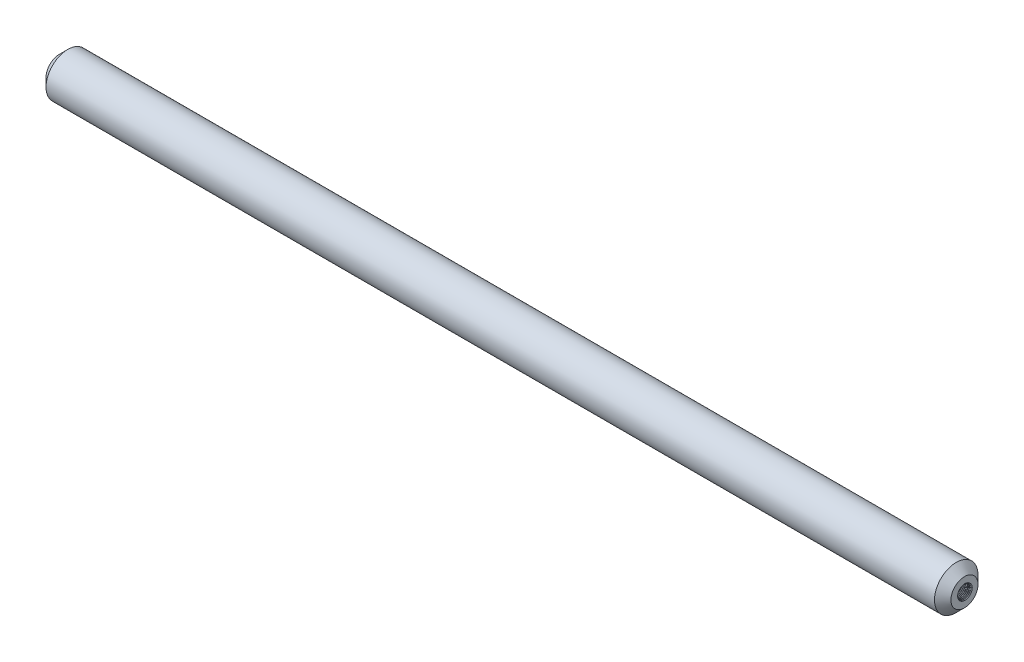
SolidWorks part; units mm, degrees
ref_plane "Front Plane" through (0, 0, 0) normal (0, 0, 1) x (1, 0, 0)
ref_plane "Top Plane" through (0, 0, 0) normal (0, 1, 0) x (1, 0, 0)
ref_plane "Right Plane" through (0, 0, 0) normal (1, 0, 0) x (0, 0, -1)
sketch "Sketch1" plane through (0, 0, 0) normal (1, 0, 0) x (0, 0, -1)
  circle A0 centre (0, 0) radius 7.9375
  dimension "D1" = 15.875
extrude "Boss-Extrude1" add sketch "Sketch1" against normal blind 330
sketch "Sketch2" plane through (0, 0, 0) normal (1, 0, 0) x (0, 0, -1)
  circle A0 centre (0, 0) radius 2.5
  dimension "D1" = 5
extrude "Cut-Extrude1" cut sketch "Sketch2" against normal blind 24
sketch "Sketch3" plane through (-330, 0, 0) normal (-1, 0, 0) x (0, 0, 1)
  circle A0 centre (0, 0) radius 2.5
  dimension "D1" = 5
extrude "Cut-Extrude2" cut sketch "Sketch3" against normal blind 24
sketch "Sketch4" plane through (0, 0, 0) normal (1, 0, 0) x (0, 0, -1)
  circle A0 centre (0, 0) radius 2.5
  dimension "D1" = 5
curve "Helix/Spiral1" pitch 0.5 height 18 radius 2.5 centre (0, 0, 0) axis (-1, 0, 0) start towards (0, 0, -1)
sketch "Sketch5" plane through (0, 0, 0) normal (1, 0, 0) x (0, 0, -1)
  line L1 (2.5, 0) -> (0, 0) construction
  circle A0 centre (0, 0) radius 2.5 construction
sketch3d "3DSketch5"
  point P0 (0, 0, -2.5)
sketch3d "3DSketch6"
  line L0 (0.2, 0, -2.5) -> (-0.2, 0, -2.5)
  line L2 (0.2, 0, -2.5) -> (-0.0014, 0, -2.8472)
  line L3 (-0.0014, 0, -2.8472) -> (-0.2, 0, -2.5)
  point P11 (0, 0, -2.5)
  dimension "D1" = 0.4
  dimension "D2" = 0.4
sweep "Cut-Sweep5" cut profiles "3DSketch6" path "Helix/Spiral1" align with end faces yes
sketch "Sketch8" plane through (-330, 0, 0) normal (-1, 0, 0) x (0, 0, 1)
  circle A0 centre (0, 0) radius 2.5
curve "Helix/Spiral3" pitch 0.5 height 18 radius 2.5 centre (-330, 0, 0) axis (1, 0, 0) start towards (0, 0, 1)
sketch "Sketch9" plane through (-330, 0, 0) normal (-1, 0, 0) x (0, 0, 1)
  line L0 (0, 0) -> (2.5, 0) construction
  circle A0 centre (0, 0) radius 2.5 construction
sketch3d "3DSketch7"
  point P0 (-330, 0, 2.5)
sketch3d "3DSketch8"
  line L0 (-329.8, 0, 2.5) -> (-330, 0, 2.8464)
  line L1 (-330.2, 0, 2.5) -> (-329.8, 0, 2.5)
  line L4 (-330, 0, 2.8464) -> (-330.2, 0, 2.5)
  point P6 (-330, 0, 2.5)
  point P7 (-330, 0, 2.5)
  dimension "D1" = 0.4
  dimension "D2" = 0.4
  dimension "D3" = 0.4
sweep "Cut-Sweep6" cut profiles "3DSketch8" path "Helix/Spiral3" align with end faces yes
chamfer "Chamfer1" distance 3 angle 45 2 edges at (-330, 0, -7.9375) (0, 0, -7.9375)
